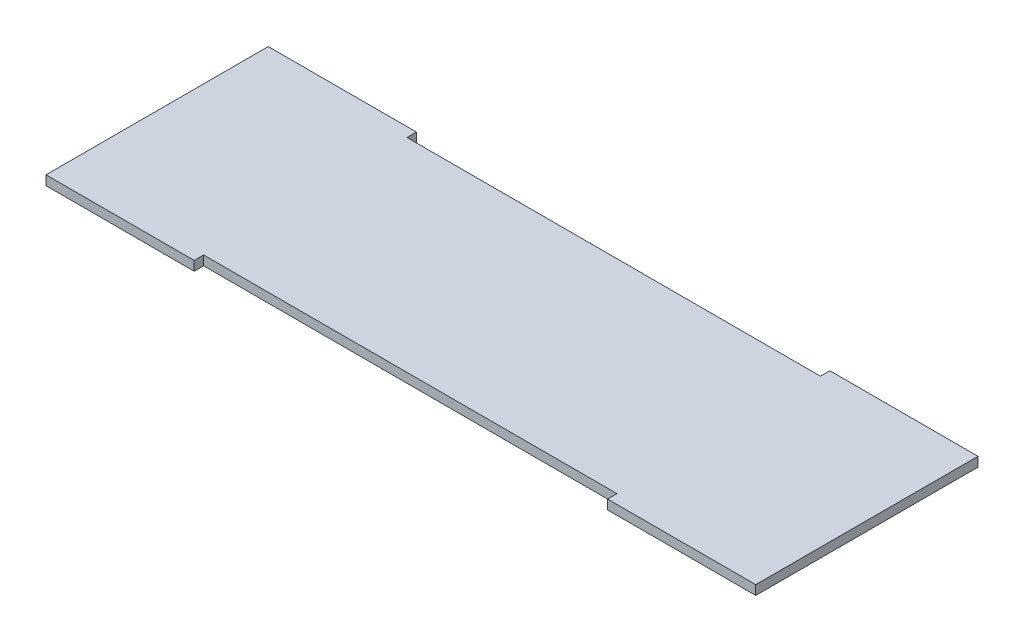
SolidWorks part; units mm, degrees
ref_plane "Front Plane" through (0, 0, 0) normal (0, 0, 1) x (1, 0, 0)
ref_plane "Top Plane" through (0, 0, 0) normal (0, 1, 0) x (1, 0, 0)
ref_plane "Right Plane" through (0, 0, 0) normal (1, 0, 0) x (0, 0, -1)
other "Default"
sketch "Sketch1" plane through (0, 0, 0) normal (0, 1, 0) x (1, 0, 0)
  line L0 (-239.5, 75) -> (-239.5, -75)
  line L1 (-239.5, -75) -> (-139.5, -75)
  line L2 (-139.5, -75) -> (-139.5, -68.65)
  line L3 (-139.5, -68.65) -> (139.5, -68.65)
  line L4 (139.5, -68.65) -> (139.5, -75)
  line L5 (139.5, -75) -> (239.5, -75)
  line L6 (239.5, -75) -> (239.5, 75)
  line L7 (239.5, 75) -> (139.5, 75)
  line L8 (139.5, 75) -> (139.5, 68.65)
  line L9 (139.5, 68.65) -> (-139.5, 68.65)
  line L10 (-139.5, 68.65) -> (-139.5, 75)
  line L11 (-139.5, 75) -> (-239.5, 75)
  point P11 (0, -68.65)
  point P13 (239.5, 0)
  dimension "D1" = 150
  dimension "D2" = 6.35
  dimension "TabWidth" = 100
  dimension "Width" = 479
extrude "Boss-Extrude1" add sketch "Sketch1" along normal mid plane 6.35
